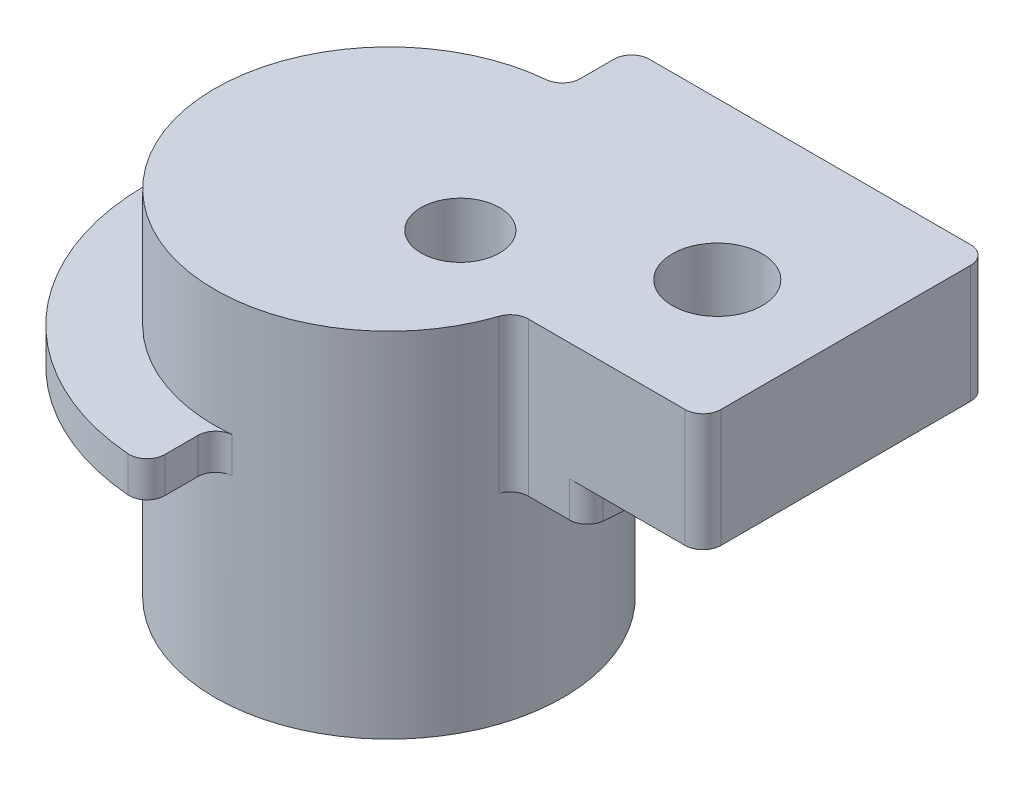
SolidWorks part; units mm, degrees
material "PET"
ref_plane "Front Plane" through (0, 0, 0) normal (1, 0, 0) x (0, 1, 0)
ref_plane "Top Plane" through (0, 0, 0) normal (0, 0, 1) x (0, 1, 0)
ref_plane "Right Plane" through (0, 0, 0) normal (0, 1, 0) x (-1, 0, 0)
sketch "Sketch2" plane through (0, 0, 0) normal (0, 0, 1) x (0, 1, 0)
  line L0 (0, 7.747) -> (0, -7.747) construction
  line L1 (15.7163, -7.747) -> (-15.7163, -7.747)
  line L2 (15.7163, -7.747) -> (15.7163, 7.747)
  line L3 (15.7163, 7.747) -> (-15.7163, 7.747)
  line L4 (-15.7163, -7.747) -> (-15.7163, 7.747)
  line L5 (15.7163, -7.747) -> (-15.7163, 7.747) construction
  line L6 (15.7163, 7.747) -> (-15.7163, -7.747) construction
  line L11 (-10.4775, 10.795) -> (-8.89, 10.795)
  line L12 (-10.4775, 10.795) -> (-10.4775, -10.795)
  line L19 (-10.4775, -10.795) -> (-8.89, -10.795)
  line L20 (-8.89, 10.795) -> (-8.89, -10.795)
  line L21 (10.4775, -10.795) -> (8.89, -10.795)
  line L22 (8.89, 10.795) -> (8.89, -10.795)
  line L23 (10.4775, 10.795) -> (8.89, 10.795)
  line L24 (10.4775, 10.795) -> (10.4775, -10.795)
  line L25 (-15.7163, 0) -> (15.7163, 0)
  point P0 (0, 0)
  point P6 (0, 0)
  point P11 (0, 0)
  point P16 (-10.4775, 0)
  dimension "D1" = 15.494
  dimension "D2" = 31.4325
  dimension "D5" = 1.5875
  dimension "D6" = 21.59
  dimension "D7" = 8.89
revolve "Revolve2" add sketch "Sketch2" angle 360 about L25 region at (-3.8735, 13.0969, 0) region at (-3.8735, 9.6838, 0) region at (-3.8735, 0, 0) region at (-9.271, 9.6838, 0) region at (-3.8735, -9.6838, 0) region at (-3.8735, -13.0969, 0) region at (-9.271, -9.6838, 0)
sketch "Sketch3" plane through (0, 0, 0) normal (0, 1, 0) x (-1, 0, 0)
  circle A0 centre (0, 0) radius 11.3381
extrude "Cut-Extrude1" cut sketch "Sketch3" against normal blind 21.336
sketch "Sketch5" plane through (0, 15.7163, 0) normal (0, 1, 0) x (-1, 0, 0)
  line L5 (0, -10.795) -> (-15.875, -10.795)
  line L6 (0, -10.795) -> (0, 1.905)
  line L7 (0, 1.905) -> (-15.875, 1.905)
  line L8 (-15.875, -10.795) -> (-15.875, 1.905)
  circle A0 centre (-3.175, 0) radius 1.75
  circle A1 centre (0, 0) radius 7.747 construction
  circle A2 centre (0, 0) radius 7.747 construction
  circle A3 centre (-3.175, 0) radius 3.35 construction
  circle A9 centre (0, 0) radius 7.747
  circle A10 centre (-10.795, -3.81) radius 2
  circle A13 centre (0, 0) radius 10.795 construction
  circle A14 centre (-10.795, -3.81) radius 3.6 construction
  circle A15 centre (0, 0) radius 10.541 construction
  point P4 (7.747, 0)
  point P13 (-3.175, 1.75)
  point P15 (-3.175, 3.35)
  point P20 (-8.795, -3.81)
  point P21 (-7.195, -3.81)
  circle M7 centre (0, 0) radius 7.747
  dimension "D1" = 3.5
  dimension "D8" = 1.6
  dimension "D3" = 4
  dimension "D7" = 15.875
  dimension "D10" = 21.082
  dimension "D2" = 3.175
  dimension "D4" = 7.62
  dimension "D5" = 1.6
  dimension "D6" = 12.7
  dimension "D9" = 3.81
  dimension "5" = 0
extrude "Cut-Extrude3" cut sketch "Sketch5" against normal blind 27.432 contours A0 region at (3.175, 15.7163, 0)
extrude "Boss-Extrude2" add sketch "Sketch5<3>" against normal up to surface (5.2387 mm away) contours L8 A10 M7 region at (7.9375, 15.7163, -10.5917) up to face at (7.747, 10.4775, 0)
sketch "Sketch5<3>" plane through (0, 15.7163, 0) normal (0, 1, 0) x (-1, 0, 0) same geometry as "Sketch5"
fillet "Fillet1" radius 0.7937 5 edges at (0, 13.0969, -10.795) (0, 13.0969, -7.747) (15.875, 13.0969, -10.795) (7.5091, 13.0969, 1.905) (15.875, 13.0969, 1.905)
sketch "Sketch6" plane through (0, 10.4775, 0) normal (0, 1, 0) x (-1, 0, 0)
  line L0 (0, 7.747) -> (0, 10.795)
  line L3 (0, -8.5038) -> (0, -10.0013)
  line L4 (-10.6256, 1.905) -> (-8.1032, 1.905)
  line L5 (0, -8.5038) -> (0, -10.0013)
  line L6 (-10.6256, 1.905) -> (-8.1032, 1.905)
  arc A0 (0.72, -7.7135) -> (-7.3501, 2.4479) centre (0, 0) ccw construction
  arc A1 (-0.6251, -10.7769) -> (-10.6256, 1.905) centre (0, 0) ccw construction
  arc A7 (0.72, -7.7135) -> (-7.3501, 2.4479) centre (0, 0) ccw
  arc A8 (0.72, -7.7135) -> (0, -8.5038) centre (0.7938, -8.5038) ccw
  arc A9 (-0.6251, -10.7769) -> (0, -10.0013) centre (-0.7937, -10.0013) ccw
  arc A10 (-0.6251, -10.7769) -> (-10.6256, 1.905) centre (0, 0) ccw
  arc A11 (-8.1032, 1.905) -> (-7.3501, 2.4479) centre (-8.1032, 2.6987) ccw
  arc A12 (0.72, -7.7135) -> (-7.3501, 2.4479) centre (0, 0) ccw
  arc A13 (0.72, -7.7135) -> (0, -8.5038) centre (0.7938, -8.5038) ccw
  arc A14 (-0.6251, -10.7769) -> (0, -10.0013) centre (-0.7937, -10.0013) ccw
  arc A15 (-0.6251, -10.7769) -> (-10.6256, 1.905) centre (0, 0) ccw
  arc A16 (-8.1032, 1.905) -> (-7.3501, 2.4479) centre (-8.1032, 2.6987) ccw
  arc M8 (-7.3501, 2.4479) -> (0.72, -7.7135) centre (0, 0) cw
  arc M12 (-0.6251, -10.7769) -> (-10.6256, 1.905) centre (0, 0) ccw
  line M13 (-10.6256, 1.905) -> (-8.1032, 1.905)
  arc M14 (-8.1032, 1.905) -> (-7.3501, 2.4479) centre (-8.1032, 2.6987) ccw
  dimension "D1" = 0
extrude "Cut-Extrude4" cut sketch "Sketch6" against normal blind 14.224 contours L0 M8 M12 M13 M14 region at (5.4587, 10.4775, 6.7219)
fillet "Fillet2" radius 0.7937 3 edges at (10.6256, 9.6838, 1.905) (0, 9.6838, 7.747) (0, 9.6838, 10.795)
